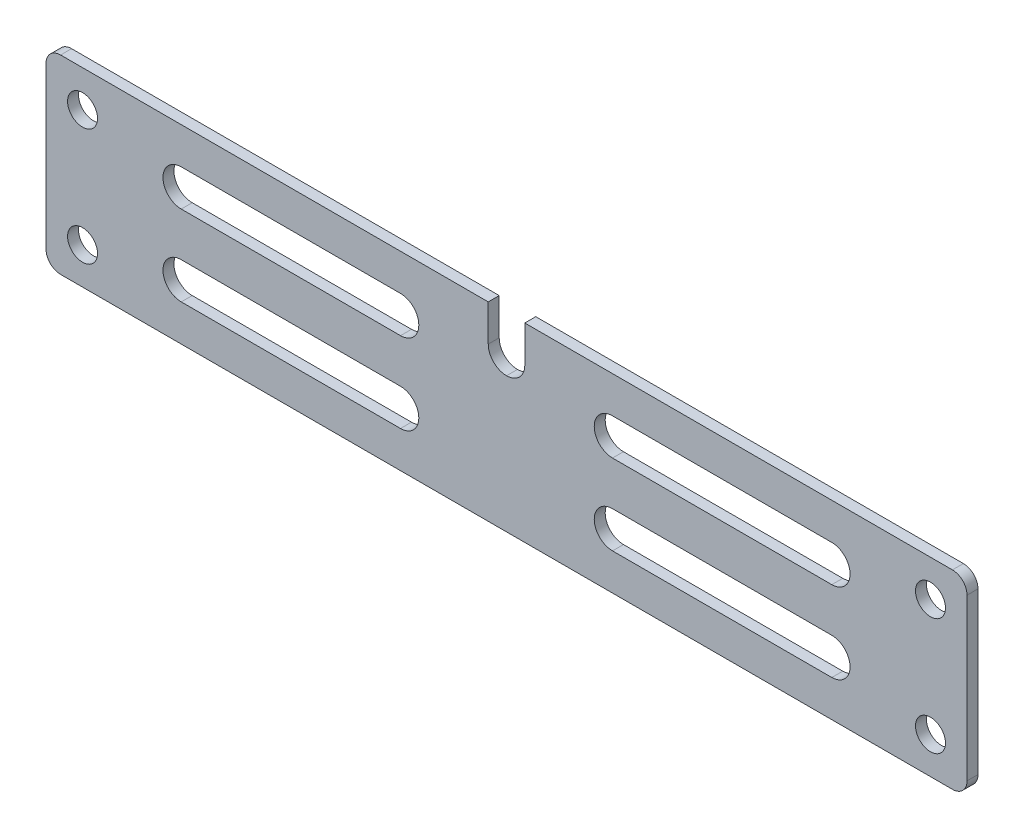
SolidWorks part; units mm, degrees
ref_plane "前视基准面" through (0, 0, 0) normal (0, 0, 1) x (1, 0, 0)
ref_plane "上视基准面" through (0, 0, 0) normal (0, 1, 0) x (1, 0, 0)
ref_plane "右视基准面" through (0, 0, 0) normal (1, 0, 0) x (0, 0, -1)
sketch "草图1" plane through (0, 0, 0) normal (0, 0, 1) x (1, 0, 0)
  line L1 (63, -13) -> (-63, -13)
  line L2 (63, -13) -> (63, 13)
  line L3 (63, 13) -> (-63, 13)
  line L4 (-63, -13) -> (-63, 13)
  line L5 (63, -13) -> (-63, 13) construction
  line L6 (63, 13) -> (-63, -13) construction
  point P0 (0, 0)
  dimension "D1" = 26
  dimension "D2" = 126
extrude "凸台-拉伸1" add sketch "草图1" along normal blind 1.5
fillet "圆角1" radius 2 4 edges at (63, 13, 0.75) (63, -13, 0.75) (-63, -13, 0.75) (-63, 13, 0.75)
sketch "草图2" plane through (0, 0, 1.5) normal (0, 0, 1) x (1, 0, 0)
  line L0 (0, 0) -> (0, 13) construction
  line L1 (61, 13) -> (-61, 13) construction
  line L2 (-2.5, 5.5) -> (2.5, 5.5)
  line L3 (-2.5, 5.5) -> (-2.5, 20.5)
  line L4 (2.5, 5.5) -> (2.5, 20.5)
  line L5 (-2.5, 20.5) -> (2.5, 20.5)
  line L6 (-2.5, 5.5) -> (2.5, 20.5) construction
  line L7 (2.5, 5.5) -> (-2.5, 20.5) construction
  dimension "D1" = 5
  dimension "D2" = 7.5
extrude "切除-拉伸1" cut sketch "草图2" against normal through all
fillet "圆角2" radius 2.5 2 edges at (2.5, 5.5, 0.75) (-2.5, 5.5, 0.75)
sketch "草图3" plane through (0, 0, 1.5) normal (0, 0, 1) x (1, 0, 0)
  line L0 (-44.5, 5.5) -> (-14.5, 5.5) construction
  line L1 (-44.5, 8) -> (-14.5, 8)
  line L2 (-44.5, 3) -> (-14.5, 3)
  line L3 (14.5, 5.5) -> (44.5, 5.5) construction
  line L4 (14.5, 8) -> (44.5, 8)
  line L5 (14.5, 3) -> (44.5, 3)
  line L6 (14.5, -5.5) -> (44.5, -5.5) construction
  line L7 (14.5, -3) -> (44.5, -3)
  line L8 (14.5, -8) -> (44.5, -8)
  line L9 (-44.5, -5.5) -> (-14.5, -5.5) construction
  line L10 (-44.5, -3) -> (-14.5, -3)
  line L11 (-44.5, -8) -> (-14.5, -8)
  line L12 (0, 0) -> (0, 36.2119) construction
  line L13 (0, 0) -> (50000, 0) construction
  arc A0 (-44.5, 8) -> (-44.5, 3) centre (-44.5, 5.5) ccw
  arc A1 (-14.5, 3) -> (-14.5, 8) centre (-14.5, 5.5) ccw
  arc A2 (14.5, 8) -> (14.5, 3) centre (14.5, 5.5) ccw
  arc A3 (44.5, 3) -> (44.5, 8) centre (44.5, 5.5) ccw
  arc A4 (14.5, -3) -> (14.5, -8) centre (14.5, -5.5) ccw
  arc A5 (44.5, -8) -> (44.5, -3) centre (44.5, -5.5) ccw
  arc A6 (-44.5, -3) -> (-44.5, -8) centre (-44.5, -5.5) ccw
  arc A7 (-14.5, -8) -> (-14.5, -3) centre (-14.5, -5.5) ccw
  point P2 (-29.5, 5.5)
  point P11 (29.5, 5.5)
  point P18 (29.5, -5.5)
  point P25 (-29.5, -5.5)
  dimension "D2" = 2.5
  dimension "D1" = 30
  dimension "D5" = 29
  dimension "D6" = 11
  dimension "D3" = 2
  dimension "D4" = 2
extrude "切除-拉伸2" cut sketch "草图3" against normal through all
sketch "草图4" plane through (0, 0, 1.5) normal (0, 0, 1) x (1, 0, 0)
  line L0 (-58, 8) -> (-58, -8) construction
  line L1 (-58, -8) -> (58, -8) construction
  line L2 (58, -8) -> (58, 8) construction
  line L3 (58, 8) -> (-58, 8) construction
  line L4 (0, 0) -> (-50000, 0) construction
  line L5 (0, 0) -> (0, 50000) construction
  circle A0 centre (58, -8) radius 2.05
  circle A1 centre (58, 8) radius 2.05
  circle A2 centre (-58, 8) radius 2.05
  circle A3 centre (-58, -8) radius 2.05
  point P13 (0, 0)
  point P14 (0, 0)
  dimension "D1" = 4.1
  dimension "D2" = 116
  dimension "D3" = 16
extrude "切除-拉伸3" cut sketch "草图4" against normal through all
